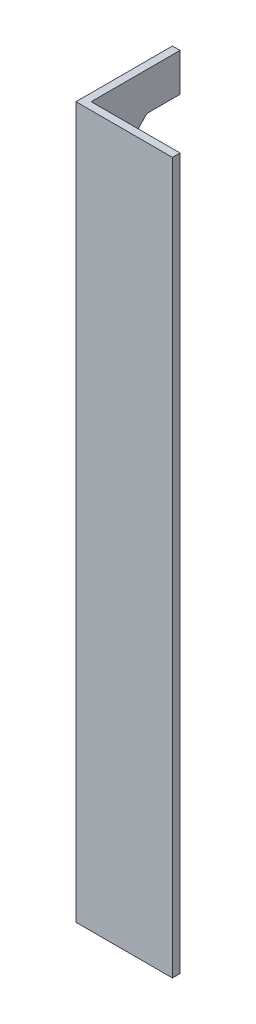
SolidWorks part; units mm, degrees
ref_plane "Alzado" through (0, 0, 0) normal (0, 0, 1) x (1, 0, 0)
ref_plane "Planta" through (0, 0, 0) normal (0, 1, 0) x (1, 0, 0)
ref_plane "Vista lateral" through (0, 0, 0) normal (1, 0, 0) x (0, 0, -1)
sketch "Croquis1" plane through (0, 0, 0) normal (0, 1, 0) x (1, 0, 0)
  line L0 (0, 0) -> (0, 38)
  line L1 (0, 0) -> (38, 0)
  line L2 (3, 3) -> (38, 3)
  line L3 (3, 3) -> (3, 38)
  line L4 (0, 38) -> (3, 38)
  line L5 (38, 3) -> (38, 0)
  dimension "D1" = 38
  dimension "D2" = 3
extrude "Saliente-Extruir1" add sketch "Croquis1" along normal blind 280
sketch "Croquis2" plane through (0, 0, 0) normal (-1, 0, 0) x (0, 0, 1)
  line L0 (-15, 0) -> (-15, 280) construction
  line L1 (-38, 0) -> (0, 0) construction
  line L2 (-38, 280) -> (0, 280) construction
  line L3 (-38, 280) -> (-38, 0) construction
  line L4 (0, 280) -> (0, 0) construction
  line L5 (-38, 15) -> (-15, 15)
  line L6 (-38, 280) -> (-38, 0) construction
  line L7 (-15, 15) -> (-15, 265)
  line L8 (-15, 265) -> (-38, 265)
  line L9 (-38, 15) -> (-38, 265)
  dimension "D1" = 15
  dimension "D2" = 15
  dimension "D3" = 15
extrude "Cortar-Extruir1" cut sketch "Croquis2" against normal up to surface (3 mm away) up to face at (3, 140, -20.5)
chamfer "Chaflán1" distance 10 angle 45 2 edges at (1.5, 15, -15) (1.5, 265, -15)
sketch "Croquis3" plane through (0, 0, 0) normal (0, 0, 1) x (1, 0, 0)
  circle A0 centre (18, 179.5) radius 5 construction
  circle A1 centre (18, 179.5) radius 5
